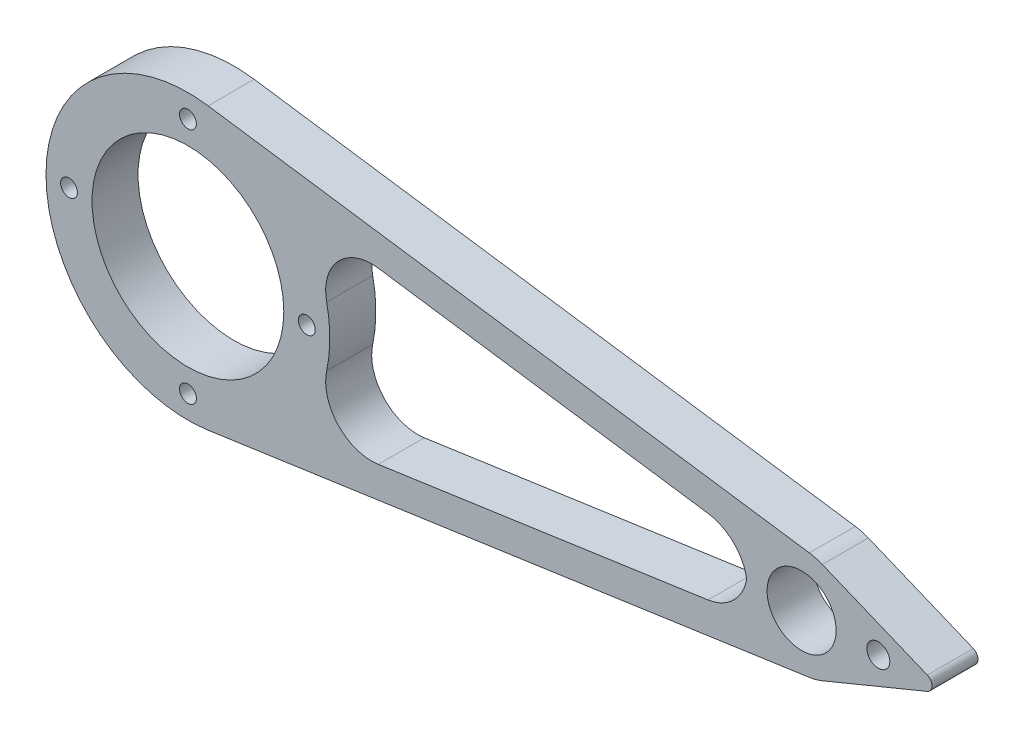
SolidWorks part; units mm, degrees
ref_plane "Plan de face" through (0, 0, 0) normal (0, 0, 1) x (1, 0, 0)
ref_plane "Plan de dessus" through (0, 0, 0) normal (0, 1, 0) x (1, 0, 0)
ref_plane "Plan de droite" through (0, 0, 0) normal (1, 0, 0) x (0, 0, -1)
sketch "Esquisse1" plane through (0, 0, 0) normal (0, 0, 1) x (1, 0, 0)
  circle A0 centre (0, 0) radius 15.5 construction
  circle A1 centre (0, 15.5) radius 1.1
  circle A2 centre (15.5, 0) radius 1.1
  circle A3 centre (0, -15.5) radius 1.1
  circle A4 centre (-15.5, 0) radius 1.1
  circle A5 centre (0, 0) radius 12.5
  circle A6 centre (0, 0) radius 18.5
  point P14 (0, 0)
  dimension "D1" = 31
  dimension "D2" = 2.2
  dimension "D4" = 3
  dimension "D5" = 3
  dimension "D3" = 4
extrude "Boss.-Extru.1" add sketch "Esquisse1" along normal blind 6
sketch "Esquisse2" plane through (0, 0, 6) normal (0, 0, 1) x (1, 0, 0)
  line L0 (0, 0) -> (80, 0) construction
  line L1 (2.6362, 18.3112) -> (81.0118, 7.0275)
  line L2 (2.6362, -18.3112) -> (81.0118, -7.0275)
  circle A0 centre (80, 0) radius 4.5
  arc A1 (81.0118, -7.0275) -> (81.0118, 7.0275) centre (80, 0) ccw
  circle A2 centre (0, 0) radius 18.5 construction
  arc A3 (2.6362, -18.3112) -> (2.6362, 18.3112) centre (0, 0) ccw
  dimension "D1" = 9
  dimension "D2" = 2.6
  dimension "D3" = 80
extrude "Boss.-Extru.2" add sketch "Esquisse2" against normal blind 6
sketch "Esquisse3" plane through (0, 0, 6) normal (0, 0, 1) x (1, 0, 0)
  line L0 (13.4381, 12.7148) -> (74.1194, 3.9786)
  line L1 (81.0118, 7.0275) -> (2.6362, 18.3112) construction
  line L2 (0, 0) -> (80, 0) construction
  line L3 (13.4381, -12.7148) -> (74.1194, -3.9786)
  arc A0 (13.4381, -12.7148) -> (13.4381, 12.7148) centre (0, 0) ccw
  arc A1 (74.1194, 3.9786) -> (74.1194, -3.9786) centre (80, 0) ccw
  dimension "D1" = 4
extrude "Enlèv. mat.-Extru.1" cut sketch "Esquisse3" against normal through all
fillet "Congé1" radius 6 4 edges at (74.1194, -3.9786, 3) (74.1194, 3.9786, 3) (13.4381, -12.7148, 3) (13.4381, 12.7148, 3)
sketch "Esquisse4" plane through (0, 0, 6) normal (0, 0, 1) x (1, 0, 0)
  line L0 (80, 0) -> (96, 0) construction
  line L1 (82.7069, 6.5638) -> (96.3813, 0.9245)
  line L2 (82.7069, -6.5638) -> (96.3813, -0.9245)
  arc A0 (81.0118, -7.0275) -> (81.0118, 7.0275) centre (80, 0) ccw construction
  arc A1 (82.7069, -6.5638) -> (82.7069, 6.5638) centre (80, 0) ccw
  arc A2 (96.3813, -0.9245) -> (96.3813, 0.9245) centre (96, 0) ccw
  circle A3 centre (90, 0) radius 1.5
  dimension "D1" = 2
  dimension "D3" = 3
  dimension "D2" = 16
  dimension "D4" = 10
extrude "Boss.-Extru.3" add sketch "Esquisse4" against normal blind 6
